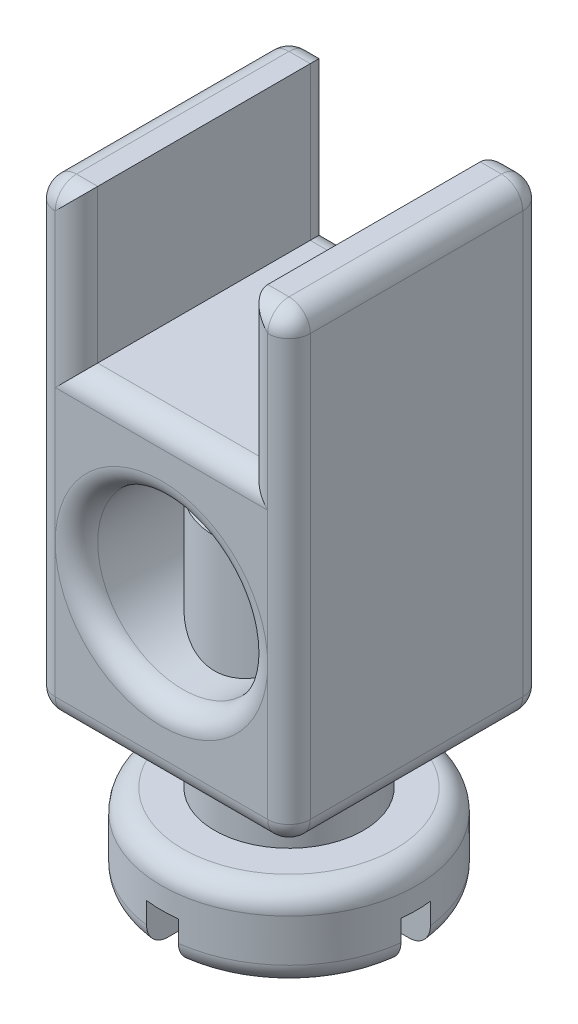
SolidWorks part; units mm, degrees
ref_plane "Front Plane" through (0, 0, 0) normal (0, 0, 1) x (1, 0, 0)
ref_plane "Top Plane" through (0, 0, 0) normal (0, 1, 0) x (1, 0, 0)
ref_plane "Right Plane" through (0, 0, 0) normal (1, 0, 0) x (0, 0, -1)
sketch "Sketch1" plane through (0, 0, 0) normal (0, 1, 0) x (1, 0, 0)
  line L1 (-3, 3) -> (3, 3)
  line L2 (-3, 3) -> (-3, -3)
  line L3 (-3, -3) -> (3, -3)
  line L4 (3, 3) -> (3, -3)
  line L5 (-3, 3) -> (3, -3) construction
  line L6 (-3, -3) -> (3, 3) construction
  point P0 (0, 0)
  dimension "D1" = 6
  dimension "D2" = 6
extrude "Boss-Extrude1" add sketch "Sketch1" along normal blind 14.5
sketch "Sketch2" plane through (0, 14.5, 0) normal (0, 1, 0) x (1, 0, 0)
  line L0 (0, 3) -> (0, -3) construction
  line L1 (3, 3) -> (-3, 3) construction
  line L2 (-3, -3) -> (3, -3) construction
  line L3 (-2, 0) -> (2, 0) construction
  line L4 (-2, -3) -> (-2, 3) construction
  line L5 (2, -3) -> (2, 3) construction
  line L7 (2, 3) -> (-2, 3)
  line L8 (2, 3) -> (2, -3)
  line L9 (2, -3) -> (-2, -3)
  line L10 (-2, 3) -> (-2, -3)
  point P10 (0, 0)
  point P14 (-2, 0)
  point P17 (2, 0)
  dimension "D1" = 2
extrude "Cut-Extrude1" cut sketch "Sketch2" against normal blind 3.6
sketch "Sketch3" plane through (0, 0, 0) normal (0, -1, 0) x (1, 0, 0)
  line L1 (-3, 3) -> (3, 3)
  line L2 (-3, 3) -> (-3, -3)
  line L3 (-3, -3) -> (3, -3)
  line L4 (3, 3) -> (3, -3)
  circle A0 centre (0, 0) radius 3
  line M1 (3, -3) -> (3, 3)
  line M2 (3, 3) -> (-3, 3)
  line M3 (-3, 3) -> (-3, -3)
  line M4 (-3, -3) -> (3, -3)
extrude "Cut-Extrude2" cut sketch "Sketch3" against normal blind 3.6 contours A0 L2 M4 | A0 L3 M1 | A0 L4 M2 | A0 L1 M3 region at (-2.3299, 0, 2.3299) region at (2.3299, 0, 2.3299) region at (-2.3299, 0, -2.3299) region at (2.3299, 0, -2.3299)
sketch "Sketch4" plane through (0, 0, 0) normal (0, -1, 0) x (1, 0, 0)
  circle A0 centre (0, 0) radius 1.75
  circle A1 centre (0, 0) radius 3
  dimension "D1" = 3.5
extrude "Cut-Extrude3" cut sketch "Sketch4" against normal blind 1.6 from offset 2 offset against normal yes
sketch "Sketch5" plane through (0, 0, 3) normal (0, 0, 1) x (1, 0, 0)
  line L0 (0, 10.9) -> (0, 3.6) construction
  line L1 (-2, 10.9) -> (2, 10.9) construction
  line L2 (-1.75, 3.6) -> (1.75, 3.6) construction
  circle A0 centre (0, 7.25) radius 2
extrude "Cut-Extrude4" cut sketch "Sketch5" against normal blind 5
fillet "Fillet1" radius 0.5 2 edges at (0, 0, -3) (0, 2, -3)
fillet "Fillet3" radius 0.5 21 edges at (-3, 14.5, 0) (-3, 3.6, 0) (2.5, 14.5, -3) (2, 12.7, -3) (0, 10.9, -3) (-2, 12.7, -3) (-2.5, 14.5, -3) (-3, 9.05, -3) (0, 3.6, -3) (3, 14.5, 0) (3, 9.05, -3) (3, 3.6, 0) (-2.5, 14.5, 3) (-2, 12.7, 3) (0, 10.9, 3) (2, 12.7, 3) (2.5, 14.5, 3) (3, 9.05, 3) (0, 3.6, 3) (-3, 9.05, 3) (2, 7.25, 3)
sketch "Sketch6" plane through (0, 0, 0) normal (0, -1, 0) x (1, 0, 0)
  line L0 (-2.5, 3) -> (2.5, 3) construction
  line L1 (0.3756, -3) -> (-0.3756, -3)
  line L2 (0.3756, -3) -> (0.3756, 3)
  line L3 (0.3756, 3) -> (-0.3756, 3)
  line L4 (-0.3756, -3) -> (-0.3756, 3)
  line L5 (0.3756, -3) -> (-0.3756, 3) construction
  line L6 (0.3756, 3) -> (-0.3756, -3) construction
  point P0 (0, 0)
extrude "Cut-Extrude5" cut sketch "Sketch6" against normal blind 1
sketch "Sketch7" plane through (0, 0, 0) normal (0, -1, 0) x (1, 0, 0)
  line L1 (-3.9702, 0.3473) -> (3.9702, 0.3473)
  line L2 (-3.9702, 0.3473) -> (-3.9702, -0.3473)
  line L3 (-3.9702, -0.3473) -> (3.9702, -0.3473)
  line L4 (3.9702, 0.3473) -> (3.9702, -0.3473)
  line L5 (-3.9702, 0.3473) -> (3.9702, -0.3473) construction
  line L6 (-3.9702, -0.3473) -> (3.9702, 0.3473) construction
  point P0 (0, 0)
extrude "Cut-Extrude6" cut sketch "Sketch7" against normal blind 1
sketch "Sketch8" plane through (0, 1, 0) normal (0, -1, 0) x (1, 0, 0)
  circle A0 centre (0, 0) radius 1.75
extrude "Boss-Extrude2" add sketch "Sketch8" against normal blind 7
